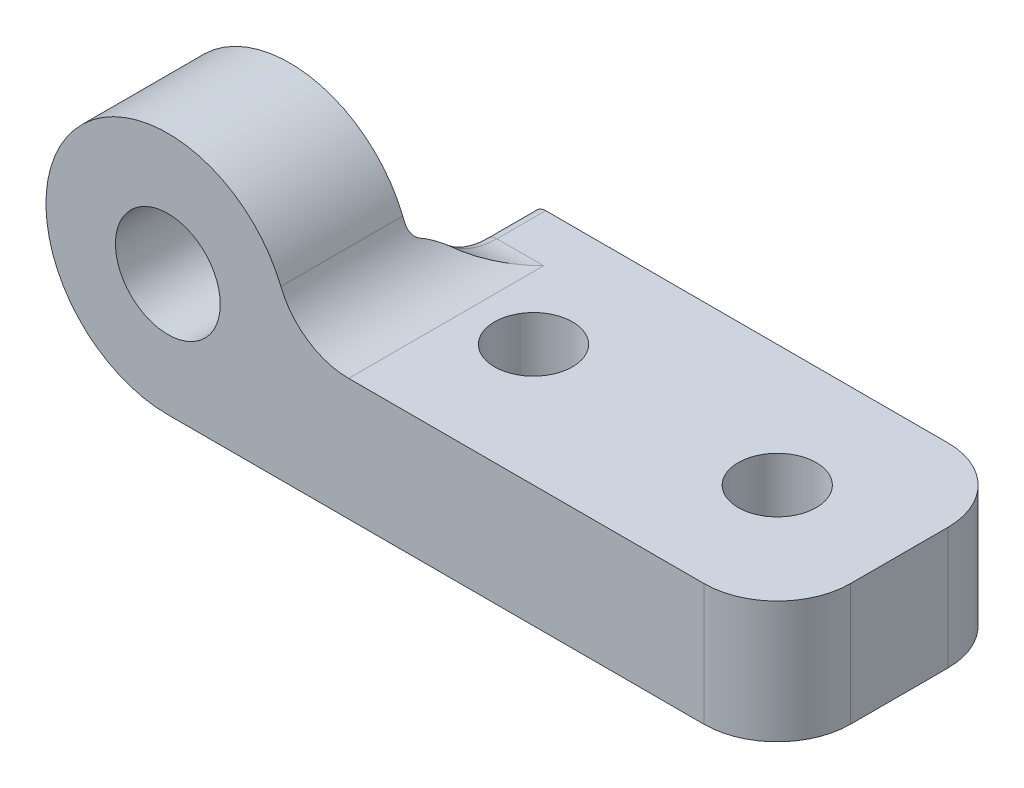
SolidWorks part; units mm, degrees
material "ﾎﾟﾘｴﾁﾚﾝｲﾐﾝ(PEI)"
ref_plane "正面" through (0, 0, 0) normal (0, 0, 1) x (1, 0, 0)
ref_plane "平面" through (0, 0, 0) normal (0, 1, 0) x (1, 0, 0)
ref_plane "右側面" through (0, 0, 0) normal (1, 0, 0) x (0, 0, -1)
sketch "ｽｹｯﾁ1" plane through (0, 0, 0) normal (0, 0, 1) x (1, 0, 0)
  circle A0 centre (0, 0) radius 5
  circle A1 centre (0, 0) radius 2.15
  dimension "D1" = 10
  dimension "D2" = 4.3
extrude "ﾎﾞｽ - 押し出し1" add sketch "ｽｹｯﾁ1" along normal blind 5
sketch "ｽｹｯﾁ2" plane through (0, 0, 0) normal (0, 1, 0) x (1, 0, 0)
  line L0 (-5, -5) -> (5, -5) construction
  line L1 (0, -5) -> (25, -5)
  line L2 (0, -5) -> (0, 5)
  line L3 (0, 5) -> (25, 5)
  line L4 (25, -5) -> (25, 5)
  line L5 (25, 0) -> (5, 0) construction
  line L6 (0, 0) -> (5, 0)
  line L7 (0, 0) -> (0, 5)
  line L8 (0, 5) -> (5, 5)
  line L9 (5, 0) -> (5, 5)
  line L10 (5, -5) -> (5, 0) construction
  circle A0 centre (10, 0) radius 1.6
  circle A1 centre (20, 0) radius 1.6
  dimension "D3" = 5
  dimension "D4" = 3.2
  dimension "D5" = 3.2
  dimension "D6" = 10
  dimension "D1" = 5
  dimension "D2" = 10
  dimension "D7" = 25
extrude "ﾎﾞｽ - 押し出し2" add sketch "ｽｹｯﾁ2" along normal blind 5 from offset 5 contours L4 L5 A1 A0 L6 L2 L1 | L5 L4 L3 L9 A0 A1 region at (12.3281, 0, 2.6252) region at (15, 0, -2.6593) offset against normal yes
sketch "ｽｹｯﾁ3" plane through (0, 0, 5) normal (0, 0, 1) x (1, 0, 0)
  circle A0 centre (0, 0) radius 2.15
  dimension "D1" = 4.3
extrude "ｶｯﾄ - 押し出し1" cut sketch "ｽｹｯﾁ3" against normal blind 10
fillet "ﾌｨﾚｯﾄ6" radius 3 1 edges at (5, 0, 2.5)
fillet "ﾌｨﾚｯﾄ7" radius 3 1 edges at (6.2081, 0, 0)
fillet "ﾌｨﾚｯﾄ8" radius 0.5 2 edges at (5, 0, -4) (5, 0.3228, -1.6462)
fillet "ﾌｨﾚｯﾄ9" radius 0.5 1 edges at (5, -5, -2.5)
fillet "ﾌｨﾚｯﾄ10" radius 0.5 3 edges at (5.1464, -4.8536, 0) (5, -1.6514, 0)
fillet "ﾌｨﾚｯﾄ12" radius 3 2 edges at (25, -2.5, 5) (25, -2.5, -5)
